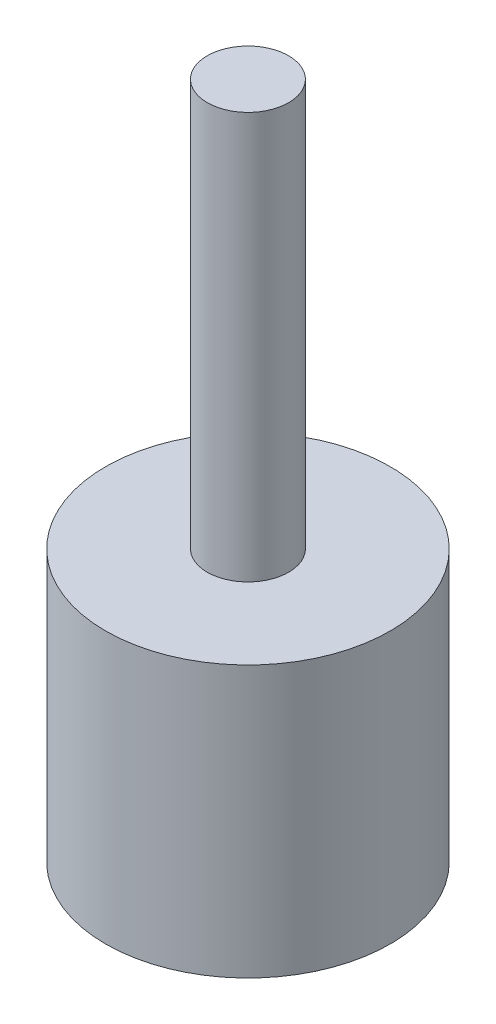
SolidWorks part; units mm, degrees
ref_plane "Front Plane" through (0, 0, 0) normal (0, 0, 1) x (1, 0, 0)
ref_plane "Top Plane" through (0, 0, 0) normal (0, 1, 0) x (1, 0, 0)
ref_plane "Right Plane" through (0, 0, 0) normal (1, 0, 0) x (0, 0, -1)
sketch "Sketch1" plane through (0, 0, 0) normal (0, 1, 0) x (1, 0, 0)
  circle A0 centre (0, 0) radius 5.25
  dimension "D1" = 10.5
extrude "Boss-Extrude1" add sketch "Sketch1" along normal blind 10
sketch "Sketch2" plane through (0, 10, 0) normal (0, 1, 0) x (1, 0, 0)
  circle A0 centre (0, 0) radius 1.5
  dimension "D1" = 3
extrude "Boss-Extrude2" add sketch "Sketch2" along normal blind 15
sketch "Sketch3" plane through (0, 0, 0) normal (0, -1, 0) x (1, 0, 0)
  line L1 (4, 0) -> (2, 3.4641)
  line L2 (2, 3.4641) -> (-2, 3.4641)
  line L3 (-2, 3.4641) -> (-4, 0)
  line L4 (-4, 0) -> (-2, -3.4641)
  line L5 (-2, -3.4641) -> (2, -3.4641)
  line L6 (2, -3.4641) -> (4, 0)
  circle A0 centre (0, 0) radius 3.4641 construction
  dimension "D1" = 4
extrude "Cut-Extrude1" cut sketch "Sketch3" against normal blind 8
ref_axis "Axis1" through (0, 10, 0) along (0, -1, 0)
